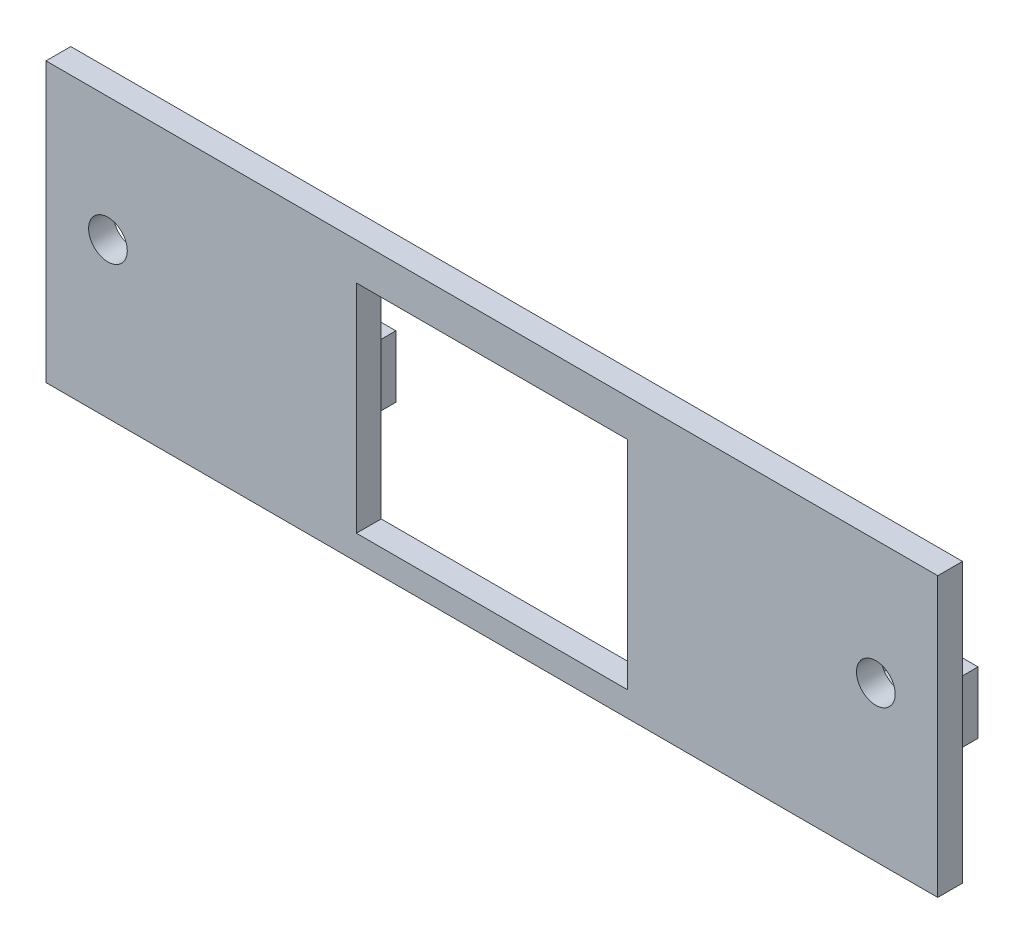
SolidWorks part; units mm, degrees
ref_plane "Front Plane" through (0, 0, 0) normal (0, 0, 1) x (1, 0, 0)
ref_plane "Top Plane" through (0, 0, 0) normal (0, 1, 0) x (1, 0, 0)
ref_plane "Right Plane" through (0, 0, 0) normal (1, 0, 0) x (0, 0, -1)
sketch "Sketch1" plane through (0, 0, 0) normal (0, 0, 1) x (1, 0, 0)
  line L0 (0, -55) -> (0, 55) construction
  line L1 (-28.8, 18) -> (28.8, 18)
  line L2 (-28.8, 18) -> (-28.8, 0)
  line L3 (-28.8, 0) -> (28.8, 0)
  line L4 (28.8, 18) -> (28.8, 0)
  line L5 (55, 0) -> (-55, 0) construction
  line L6 (-34.1699, 10) -> (46.6159, 10) construction
  circle A0 centre (-24.8, 10) radius 1.25
  circle A1 centre (24.8, 10) radius 1.25
  dimension "D1" = 57.6
  dimension "D2" = 18
  dimension "D3" = 28.8
  dimension "D4" = 0
  dimension "D5" = 10
  dimension "D6" = 24.8
  dimension "D7" = 24.8
extrude "Boss-Extrude1" add sketch "Sketch1" along normal blind 1.6
ref_plane "PCB top" through (0, 1.6, 0) normal (0, 1, 0) x (1, 0, 0)
sketch "Sketch7" plane through (0, 1.6, 0) normal (0, 1, 0) x (1, 0, 0)
  line L0 (0, -0.88) -> (0, 0.88) construction
  line L1 (-28.8, 75.2) -> (28.8, 75.2) construction
  line L2 (-28.8, 75.2) -> (-28.8, 0.2) construction
  line L3 (-28.8, 0.2) -> (28.8, 0.2) construction
  line L4 (28.8, 75.2) -> (28.8, 0.2) construction
  line L5 (-9.9, 0) -> (9.9, 0) construction
  line L6 (-22.8, 75.2) -> (-22.8, 0) construction
  line L7 (22.8, 75.2) -> (22.8, 0) construction
  line L9 (-22.8, 0) -> (-14.8, 0)
  line L10 (-22.8, 0) -> (-22.8, 7)
  line L11 (-22.8, 7) -> (-14.8, 7)
  line L12 (-14.8, 0) -> (-14.8, 7)
  line L13 (22.8, 0) -> (14.8, 0)
  line L14 (22.8, 0) -> (22.8, 7)
  line L15 (22.8, 7) -> (14.8, 7)
  line L16 (14.8, 0) -> (14.8, 7)
  circle A0 centre (-18.8, 4.2) radius 1.3
  circle A1 centre (18.8, 4.2) radius 1.3
  point P22 (0, 0)
  dimension "D14" = 2.6
  dimension "D15" = 2.6
  dimension "D1" = 28.8
  dimension "D2" = 28.8
  dimension "D3" = 0.2
  dimension "D4" = 75
  dimension "D5" = 6
  dimension "D6" = 6
  dimension "8" = 8
  dimension "D8" = 7
  dimension "D9" = 8
  dimension "D10" = 7
  dimension "D11" = 4
  dimension "D7" = 4
  dimension "D12" = 4
  dimension "D13" = 4
extrude "Boss-Extrude3" add sketch "Sketch7" along normal blind 4 separate body
sketch "Sketch8" plane through (0, 0, 0) normal (0, 0, 1) x (1, 0, 0)
  line L0 (0, -4.73) -> (0, 4.73) construction
  line L1 (-8.75, 15.6) -> (8.75, 15.6)
  line L2 (-8.75, 15.6) -> (-8.75, 1.6)
  line L3 (-8.75, 1.6) -> (8.75, 1.6)
  line L4 (8.75, 15.6) -> (8.75, 1.6)
  line L5 (4.73, 1.6) -> (-4.73, 1.6) construction
  dimension "D1" = 17.5
  dimension "D2" = 14
  dimension "D3" = 8.75
extrude "Cut-Extrude1" cut sketch "Sketch8" against normal through all both and the other way through all
combine bodies "Combine1" operation type add bodies to combine 106 108 107
fillet "Fillet1" radius 0.5 6 edges at (-14.8, 3.6, 0) (-22.8, 3.6, 0) (-18.8, 5.6, 0) (14.8, 3.6, 0) (22.8, 3.6, 0) (18.8, 5.6, 0)
equation "\"D3@Sketch1\"=57.6/2"
equation "\"D1\"= 164 / 2"
equation "\"D1@Sketch7\"=57.6/2"
equation "\"D2@Sketch7\"=\"D1@Sketch7\""
equation "\"D9@Sketch7\"=\"8@Sketch7\""
equation "\"D10@Sketch7\"=\"D8@Sketch7\""
equation "\"D7@Sketch7\"=\"D11@Sketch7\""
equation "\"D15@Sketch7\"=\"D14@Sketch7\""
equation "\"D13@Sketch7\"=\"D12@Sketch7\""
